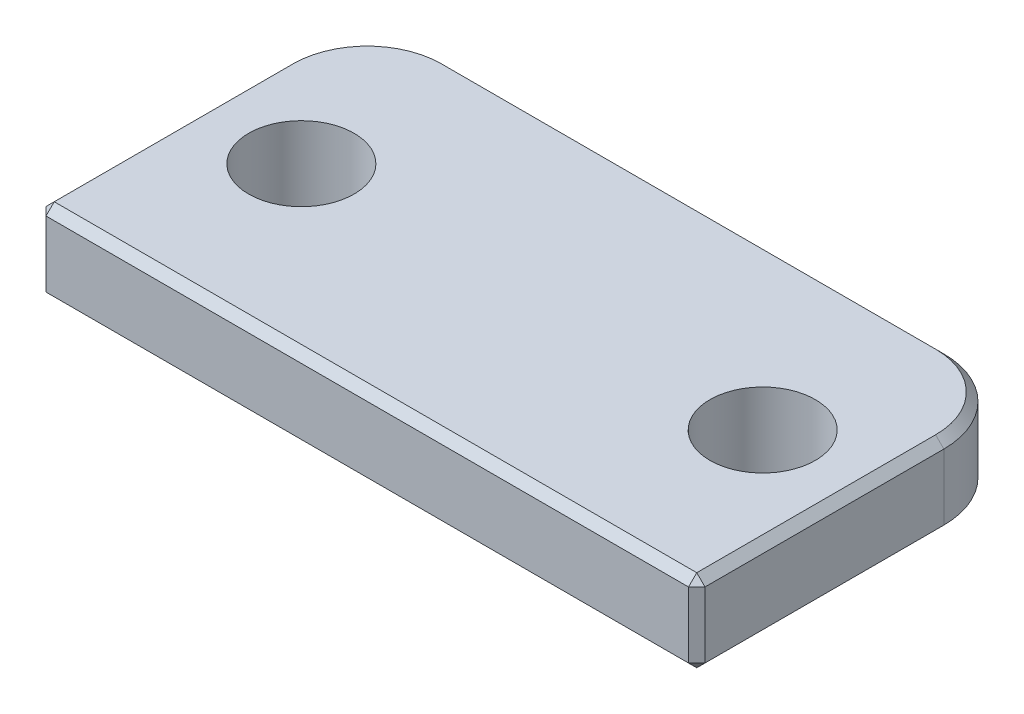
SolidWorks part; units mm, degrees
material "Plain Carbon Steel"
ref_plane "Front Plane" through (0, 0, 0) normal (0, 0, 1) x (1, 0, 0)
ref_plane "Top Plane" through (0, 0, 0) normal (0, 1, 0) x (1, 0, 0)
ref_plane "Right Plane" through (0, 0, 0) normal (1, 0, 0) x (0, 0, -1)
sketch "Sketch1" plane through (0, 0, 0) normal (0, 1, 0) x (1, 0, 0)
  line L1 (-20, -10) -> (20, -10)
  line L2 (-20, -10) -> (-20, 10)
  line L3 (-20, 10) -> (20, 10)
  line L4 (20, -10) -> (20, 10)
  line L5 (-20, -10) -> (20, 10) construction
  line L6 (-20, 10) -> (20, -10) construction
  point P0 (0, 0)
  dimension "D1" = 40
  dimension "D2" = 20
extrude "Boss-Extrude1" add sketch "Sketch1" along normal blind 5
hole_wizard "M6 Clearance Hole1" positions "Sketch4" profile "Sketch3" hole size "M6" standard "ISO" end condition through all
sketch "Sketch4" plane through (0, 5, 0) normal (0, 1, 0) x (1, 0, 0)
  line L0 (-20, 0) -> (20, 0) construction
  line L1 (-20, 10) -> (-20, -10) construction
  line L2 (20, -10) -> (20, 10) construction
  point P0 (-14, 0)
  point P2 (14, 0)
  dimension "D1" = 6
  dimension "D2" = 6
sketch "Sketch3" plane through (-14, 5, 0) normal (1, 0, 0) x (0, 0, 1)
  line L0 (0, 0) -> (0, 5)
  line L1 (0, 5) -> (3.2, 5)
  line L2 (3.2, 5) -> (3.2, 0)
  line L5 (3.2, 0) -> (0, 0)
  line L11 (0, -6.35) -> (0, 107.95) construction
  dimension "Thru Hole Dia." = 6.4
  dimension "Thru Hole Depth" = 5
fillet "Fillet1" radius 5 2 edges at (-20, 2.5, -10) (20, 2.5, -10)
chamfer "Chamfer1" distance 0.5 angle 45 14 edges at (0, 0, -10) (-20, 2.5, 10) (-20, 5, 2.5) (-20, 0, 2.5) (20, 0, 2.5) (0, 0, 10) (20, 2.5, 10) (0, 5, -10) (20, 5, 2.5) (0, 5, 10) (-18.5355, 5, -8.5355) (-18.5355, 0, -8.5355) (18.5355, 0, -8.5355) (18.5355, 5, -8.5355)
